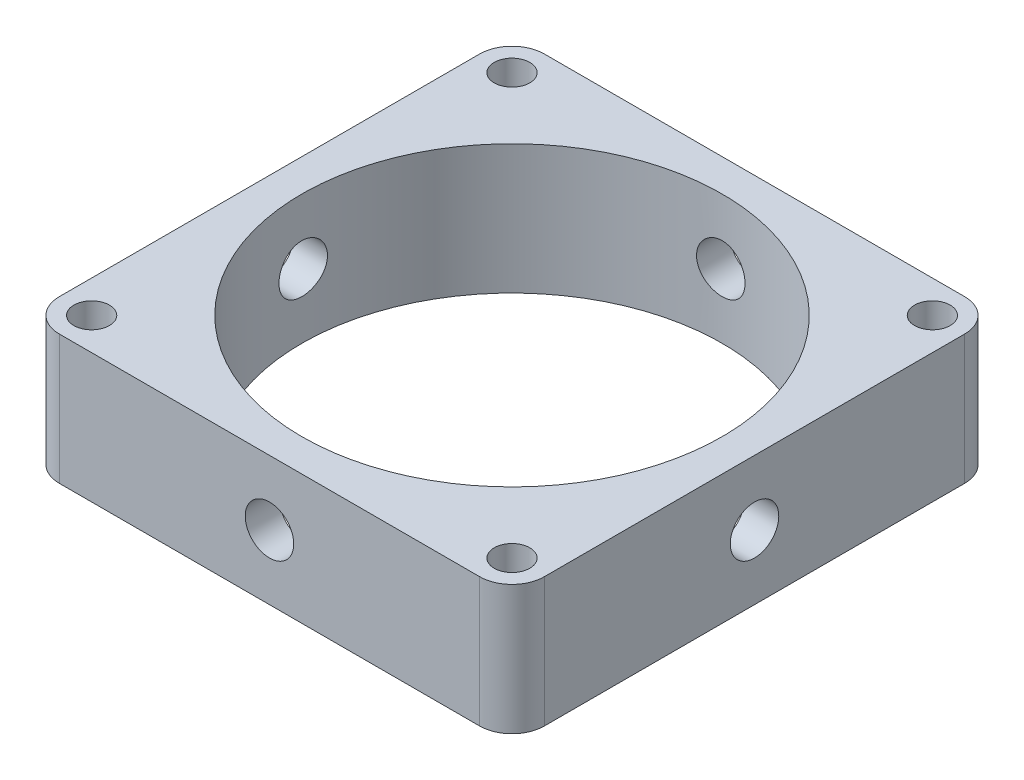
SolidWorks part; units mm, degrees
ref_plane "Front Plane" through (0, 0, 0) normal (0, 0, 1) x (1, 0, 0)
ref_plane "Top Plane" through (0, 0, 0) normal (0, 1, 0) x (1, 0, 0)
ref_plane "Right Plane" through (0, 0, 0) normal (1, 0, 0) x (0, 0, -1)
sketch "Sketch1" plane through (0, 0, 0) normal (0, 1, 0) x (1, 0, 0)
  line L1 (-38.1, -38.1) -> (38.1, -38.1)
  line L2 (-38.1, -38.1) -> (-38.1, 38.1)
  line L3 (-38.1, 38.1) -> (38.1, 38.1)
  line L4 (38.1, -38.1) -> (38.1, 38.1)
  line L5 (-38.1, -38.1) -> (38.1, 38.1) construction
  line L6 (-38.1, 38.1) -> (38.1, -38.1) construction
  circle A0 centre (33.02, 33.02) radius 2.794
  circle A1 centre (33.02, -33.02) radius 2.794
  circle A2 centre (-33.02, -33.02) radius 2.794
  circle A3 centre (-33.02, 33.02) radius 2.794
  circle A4 centre (0, 0) radius 38.1 construction
  circle A5 centre (0, 0) radius 33.02
  point P0 (0, 0)
  point P17 (0, 0)
  dimension "D3" = 5.588
  dimension "D4" = 5.08
  dimension "D1" = 76.2
  dimension "D2" = 76.2
  dimension "D6" = 5.08
  dimension "D5" = 4
extrude "Boss-Extrude1" add sketch "Sketch1" along normal blind 20.32
fillet "Fillet1" radius 5.08 4 edges at (-38.1, 10.16, -38.1) (-38.1, 10.16, 38.1) (38.1, 10.16, -38.1) (38.1, 10.16, 38.1)
sketch "Sketch2" plane through (0, 0, 38.1) normal (0, 0, 1) x (1, 0, 0)
  line L0 (0, 20.32) -> (0, 0)
  line L1 (-33.02, 20.32) -> (33.02, 20.32) construction
  circle A0 centre (0, 10.16) radius 3.81
  dimension "D1" = 7.62
extrude "Cut-Extrude1" cut sketch "Sketch2" against normal through all contours L0 A0 | A0 region at (1.617, 10.16, 38.1)
sketch "Sketch3" plane through (38.1, 0, 0) normal (1, 0, 0) x (0, 0, -1)
  line L0 (0, 0) -> (0, 20.32)
  line L1 (-33.02, 20.32) -> (33.02, 20.32) construction
  circle A0 centre (0, 10.16) radius 3.81
  dimension "D1" = 7.62
extrude "Cut-Extrude2" cut sketch "Sketch3" against normal through all contours L0 A0 | L0 A0 region at (38.1, 10.16, 1.617) region at (38.1, 10.16, -1.617)
